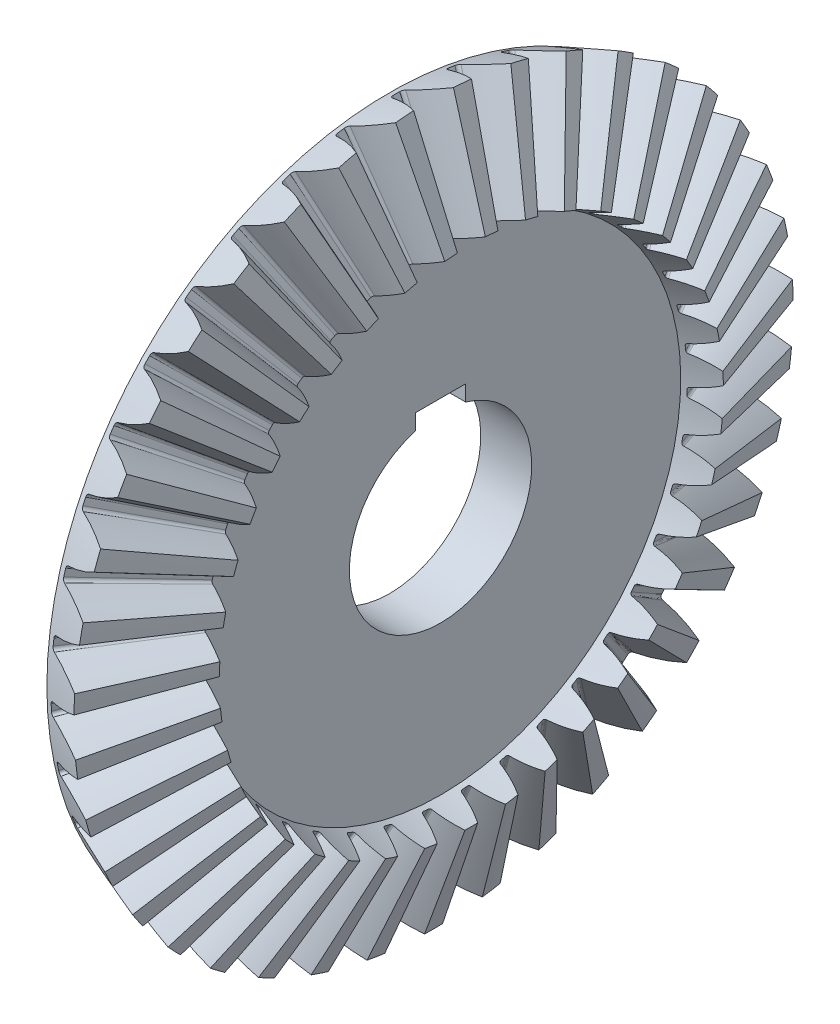
SolidWorks part; units mm, degrees
revolve "Base-Revolve" add sketch "BasProSke" angle 360 about L0
sketch "BasProSke" plane through (0, 0, 0) normal (0, 1, 0) x (1, 0, 0)
  line L0 (-10, 0) -> (60, 0) construction
  line L1 (0, 0) -> (0, 150.3279)
  line L2 (0, 0) -> (22.3607, 0)
  line L3 (22.3607, 0) -> (22.3607, 105.3574)
  line L4 (74.7476, 0) -> (3.3645, 185.5959) construction
  line L5 (0, 150.3279) -> (19.2877, 157.7462)
  line L6 (74.7476, 0) -> (16.6524, 165.2419) construction
  line L7 (74.7476, 0) -> (0, 150.3279) construction
  line L8 (19.2877, 157.7462) -> (35.8785, 110.5566)
  line L9 (35.8785, 110.5566) -> (22.3607, 105.3574)
  line L10 (14.7476, 156) -> (2.7632, 156) construction
  dimension "D1" = 300.6557
  dimension "D2" = 74.7476
  dimension "D3" = 167.1407
  dimension "D4" = 1.667
ref_plane "Plane1" through (0, 0, 0) normal (0, 0, 1) x (1, 0, 0)
ref_plane "Plane2" through (0, 0, 0) normal (0, 1, 0) x (1, 0, 0)
ref_plane "Plane3" through (0, 0, 0) normal (1, 0, 0) x (0, 0, -1)
sketch "HoldingSke" plane through (0, 0, 0) normal (0, 1, 0) x (1, 0, 0)
  line L0 (0, 0) -> (0.0971, -0.0787)
  line L1 (-15, 0) -> (100, 0) construction
  line L2 (0, 0) -> (-56.1094, 3.7267)
  line L3 (0, 0) -> (-11.863, 4.5341)
  line L4 (0, 0) -> (6.7114, 5.4348)
  line L5 (0, 0) -> (-65.5867, -24.4619)
  line L6 (0, 0) -> (-10.5278, -7.1032)
  line L7 (-56.1094, 3.7267) -> (-51.6371, 78.3405)
  line L8 (-76.2, 8) -> (-70.8, 8)
  line L9 (-71.009, 38.7566) -> (-53.1078, 45.2721)
  line L10 (-76.2, 71.12) -> (104.1128, 71.12)
  line L11 (0, 0) -> (-50, 0)
  line L12 (-76.2, 101.6) -> (-75.945, 101.6)
  line L13 (24.9733, 27.94) -> (52.9545, 28.237)
  line L14 (24.9733, 27.94) -> (24.9743, 27.94)
  line L15 (24.9733, 27.94) -> (100.3899, 30.0202)
  line L16 (-56.1094, 3.7267) -> (68.5987, -29.6887)
  circle A0 centre (0, 0) radius 40
  circle A1 centre (0, 0) radius 55
  circle A2 centre (0, 0) radius 55
  circle A3 centre (0, 0) radius 40
  dimension "Num_teeth" = 39
  dimension "Pitch_radius" = 180.3128
  dimension "Width" = 50
ref_plane "ToothPln" through (9.6439, 154.037, 0) normal (-0.359, 0.9333, 0) x (0, 0, -1)
ref_plane "ToothPln2" through (9.6324, -25.0443, 0) normal (-0.359, 0.9333, 0) x (0, 0, 1)
sketch "TooCutSke" plane through (9.6439, 154.037, 0) normal (-0.359, 0.9333, 0) x (0, 0, -1)
  line L2 (0, 150.5318) -> (146.671, -1666.3141) construction
  line L3 (0, 150.5318) -> (78.6933, -1763.3128) construction
  line L4 (0, -15.621) -> (0, 105.791) construction
  line L6 (-24.765, -10.3326) -> (21.082, -10.3326) construction
  line L7 (12.5528, -4.9623) -> (6.404, -5.2152) construction
  arc A0 (-10.4159, -13.2189) -> (10.4159, -13.2189) centre (0, 150.5318) ccw
  arc A1 (-1.4659, 7.1799) -> (1.4659, 7.1799) centre (0, 150.5318) ccw
  circle A2 centre (0, 150.5318) radius 156 construction
  circle A3 centre (0, 150.5318) radius 146.592 construction
  arc A4 (2.9549, 5.9811) -> (1.4659, 7.1799) centre (1.4813, 5.675) ccw
  arc A5 (2.9549, 5.9811) -> (10.4159, -13.2189) centre (64.0505, 18.6729) ccw
  arc A6 (-10.4159, -13.2189) -> (-2.9549, 5.9811) centre (-64.0505, 18.6729) ccw
  arc A7 (-1.4659, 7.1799) -> (-2.9549, 5.9811) centre (-1.4813, 5.675) ccw
  ellipse E0 centre (0, 46.295) end of major axis (157.7462, 46.295) minor radius 56.6276 construction
sketch "TooCutSke2" plane through (9.6324, -25.0443, 0) normal (-0.359, 0.9333, 0) x (0, 0, 1)
  line L0 (0, 0) -> (0, 68.072) construction
  line L2 (21.082, 53.9646) -> (-20.32, 53.9646) construction
  circle A0 centre (0, 69.7653) radius 0.0127
  ellipse E1 centre (0, 0) end of major axis (-150.3279, 0) minor radius 53.9646 construction
loft "ToothCut" cut profiles "TooCutSke2", "TooCutSke"
pattern_circular "TeethCuts" count 39 every 9.231 about axis through (-10, 0, 0) along (1, 0, 0) of "ToothCut"
sketch "HubSke" plane through (0, 0, 0) normal (-1, 0, 0) x (0, 0, 1)
  circle A0 centre (0, 0) radius 55
  dimension "Diameter" = 110
extrude "Hub" add sketch "HubSke" along normal blind 0.0001
sketch "BorSke" plane through (0, 0, 0) normal (1, 0, 0) x (0, 0, -1)
  circle A0 centre (0, 0) radius 40
  dimension "Diameter" = 80
extrude "Bore" cut sketch "BorSke" along normal mid plane 149.4953
sketch "KeySke" plane through (0, 0, 0) normal (1, 0, 0) x (0, 0, -1)
  line L0 (-11, 0) -> (-11, 45.4)
  line L1 (-11, 45.4) -> (11, 45.4)
  line L2 (11, 45.4) -> (11, 0)
  line L3 (0, 0) -> (0, 34) construction
  line L4 (-11, 0) -> (11, 0)
  dimension "Offset" = 45.4
extrude "Keyway" cut sketch "KeySke" along normal mid plane 149.4953
pattern_circular "Keyway2" [suppressed] count 2 every 90 about axis through (-10, 0, 0) along (1, 0, 0)
equation "' \"Module@HoldingSke\" = 6.35"
equation "' \"Num_teeth@HoldingSke\" = 20"
equation "' \"Mating_teeth@HoldingSke\" = 12"
equation "' \"Ap@HoldingSke\" =  20"
equation "' \"Ap@HoldingSke\" = 20"
equation "' \"Width@HoldingSke\" = 0.5 * 25.4"
equation "' \"Hub_dia@HoldingSke\"= 2 * 25.4"
equation "' \"Hub_dia@HoldingSke\" = 2 * 25.4"
equation "' \"Mounting_dist@HoldingSke\" = 3 * 25.4"
equation "' \"Bore@HoldingSke\" = 19"
equation "' \"T_dim@HoldingSke\" = 0.1 * 25.4"
equation "' \"Width@KeySke\" = 0.25 * 25.4"
equation "' \"Show_teeth@HoldingSke\" = 100"
equation "' \"Backlash@HoldingSke\" = 0.009 * 25.4"
equation "' \"Addendum_fac@HoldingSke\" = 1.0"
equation "' \"Dedendum_fac@HoldingSke\" = 1.188"
equation "' \"Dedendum_add@HoldingSke\" = 0.002 * 25.4"
equation "' \"Clearance_fac@HoldingSke\" = 0.188"
equation "\"Pitch@HoldingSke\" = 1 / \"Module@HoldingSke\""
equation " \"Addendum_fac@HoldingSke\" = 0.54 + 0.46 / (\"Num_teeth@HoldingSke\" /  \"Mating_teeth@HoldingSke\" ) ^ 2"
equation "' \"Addendum_fac@HoldingSke\" = 2 - (0.54 + 0.46 / (\"Mating_teeth@HoldingSke\" /  \"Num_teeth@HoldingSke\" ) ^ 2)"
equation "\"Dedendum_fac@HoldingSke\" = 2.188 - \"Addendum_fac@HoldingSke\""
equation "\"Pitch_rad@BasProSke\" = \"Num_teeth@HoldingSke\" / \"Pitch@HoldingSke\" / 2"
equation "\"Pitch_ang@BasProSke\" = atn(\"Num_teeth@HoldingSke\" / \"Mating_teeth@HoldingSke\") * (180 / 3.14159265)"
equation "\"Addendum@BasProSke\" = \"Addendum_fac@HoldingSke\" / \"Pitch@HoldingSke\""
equation "\"Dedendum_plus@BasProSke\" = (\"Dedendum_fac@HoldingSke\" / \"Pitch@HoldingSke\" + \"Dedendum_add@HoldingSke\") * 1.25"
equation "\"Face_wid@BasProSke\" = \"Width@HoldingSke\""
equation "\"Radius@TooCutSke\" = ((\"Num_teeth@HoldingSke\" + 2 * \"Addendum_fac@HoldingSke\") / \"Pitch@HoldingSke\" ) / 2"
equation "\"Overcut_dia@TooCutSke\" =  1.02 * (\"Num_teeth@HoldingSke\" + 2 * \"Addendum_fac@HoldingSke\") / \"Pitch@HoldingSke\""
equation "\"Pitch_dia@TooCutSke\" = \"Num_teeth@HoldingSke\" / \"Pitch@HoldingSke\""
equation "\"Base_dia@TooCutSke\" = \"Num_teeth@HoldingSke\" / \"Pitch@HoldingSke\" * cos((\"Ap@HoldingSke\"  * 3.14159265 / 180))"
equation "'  \"Root_dia@TooCutSke\" =  (\"Num_teeth@HoldingSke\" + 2) / \"Pitch@HoldingSke\" - 2 * (\"Addendum_fac@HoldingSke\" + \"Dedendum_fac@HoldingSke\") / \"Pitch@HoldingSke\" - \"Dedendum_add@HoldingSke\" * 2"
equation "'  \"Root_dia@TooCutSke\" = (\"Num_teeth@HoldingSke\" + 2) / \"Pitch@HoldingSke\" - 2 * (\"Addendum_fac@HoldingSke\" + \"Dedendum_fac@HoldingSke\") / \"Pitch@HoldingSke\" - \"Dedendum_add@HoldingSke\" * 2"
equation "\"Root_dia@TooCutSke\" =  \"Num_teeth@HoldingSke\" / \"Pitch@HoldingSke\" -  2 * \"Dedendum_fac@HoldingSke\" / \"Pitch@HoldingSke\" - \"Dedendum_add@HoldingSke\" * 2"
equation "\"Half_ang@TooCutSke\" = 180 / \"Num_teeth@HoldingSke\""
equation "\"Half_CT@TooCutSke\" = \"Num_teeth@HoldingSke\" / \"Pitch@HoldingSke\" * sin((3.14159265 / 2 / \"Num_teeth@HoldingSke\")) / 2 - 2 * \"Backlash@HoldingSke\" / 4"
equation "\"Flank_rad@TooCutSke\" = \"Num_teeth@HoldingSke\" / \"Pitch@HoldingSke\" / 5"
equation "\"Root_fillet@TooCutSke\" = \"Clearance_fac@HoldingSke\" / \"Pitch@HoldingSke\" + \"Dedendum_add@HoldingSke\""
equation "\"Offset@ToothPln2\"  = \"Num_teeth@HoldingSke\" / \"Pitch@HoldingSke\" / 2 / sin(atn(\"Num_teeth@HoldingSke\" / \"Mating_teeth@HoldingSke\"))"
equation "\"Dedendum_plus@TooCutSke2\" = \"Dedendum_plus@BasProSke\""
equation "\"MHD@HoldingSke\" = \"Num_teeth@HoldingSke\" / \"Pitch@HoldingSke\" - 2 * \"Dedendum_plus@BasProSke\" * cos(atn(\"Num_teeth@HoldingSke\" / \"Mating_teeth@HoldingSke\"))"
equation "\"MBD@HoldingSke\" = \"Num_teeth@HoldingSke\" / \"Pitch@HoldingSke\" - 2 * \"Dedendum_plus@BasProSke\" * cos(atn(\"Num_teeth@HoldingSke\" / \"Mating_teeth@HoldingSke\")) - 0.002 * 25.4"
equation "\"MnMD@HoldingSke\" =  \"Num_teeth@HoldingSke\" / \"Pitch@HoldingSke\" / 2 / (\"Num_teeth@HoldingSke\" / \"Mating_teeth@HoldingSke\") + \"Dedendum_plus@BasProSke\" * sin(atn(\"Num_teeth@HoldingSke\" / \"Mating_teeth@HoldingSke\"))"
equation "\"OAL@HoldingSke\" = \"MnMD@HoldingSke\""
equation "\"MHD@HoldingSke\" = ((sgn( \"MHD@HoldingSke\" - \"Hub_dia@HoldingSke\" )-1)*( \"MHD@HoldingSke\" - \"Hub_dia@HoldingSke\" ))/-2+ \"Hub_dia@HoldingSke\""
equation "\"MBD@HoldingSke\" = ((sgn( \"MBD@HoldingSke\" - \"Bore@HoldingSke\" )-1)*( \"MBD@HoldingSke\" - \"Bore@HoldingSke\" ))/-2+ \"Bore@HoldingSke\""
equation "\"Face_wid@BasProSke\" = ((sgn( \"Face_wid@BasProSke\" - \"Offset@ToothPln2\" * 0.9)-1)*( \"Face_wid@BasProSke\" - \"Offset@ToothPln2\" * 0.9))/-2+ \"Offset@ToothPln2\" * 0.9"
equation "\"OAL@HoldingSke\" = ((sgn( \"OAL@HoldingSke\" - \"Mounting_dist@HoldingSke\" )+1)*( \"OAL@HoldingSke\" - \"Mounting_dist@HoldingSke\" ))/2 + \"Mounting_dist@HoldingSke\" + 0.000002 * 25.4"
equation "\"Num_teeth@TeethCuts\" = int( \"Show_teeth@HoldingSke\" ) + 1"
equation "\"Num_teeth@TeethCuts\" = ((sgn( \"Num_teeth@TeethCuts\" - \"Num_teeth@HoldingSke\" )-1)*( \"Num_teeth@TeethCuts\" - \"Num_teeth@HoldingSke\" ))/-2+ \"Num_teeth@HoldingSke\""
equation "\"Num_teeth@TeethCuts\" = ((sgn( \"Num_teeth@TeethCuts\" - 2.0)+1)*( \"Num_teeth@TeethCuts\" - 2.0))/2 +2.0"
equation "\"Angle@TeethCuts\" = 360.0 / \"Num_teeth@HoldingSke\""
equation "\"Diameter@HubSke\" = \"MHD@HoldingSke\""
equation "\"Length@Hub\" = \"OAL@HoldingSke\" - \"MnMD@HoldingSke\" + 0.000002 * 25.4"
equation "\"Diameter@BorSke\" = \"MBD@HoldingSke\""
equation "\"D1@Bore\" = \"OAL@HoldingSke\" * 2.0"
equation "\"D1@Keyway\" = \"OAL@HoldingSke\" * 2.0"
equation "\"Offset@KeySke\" = \"T_dim@HoldingSke\" + \"MBD@HoldingSke\" / 2.0"
